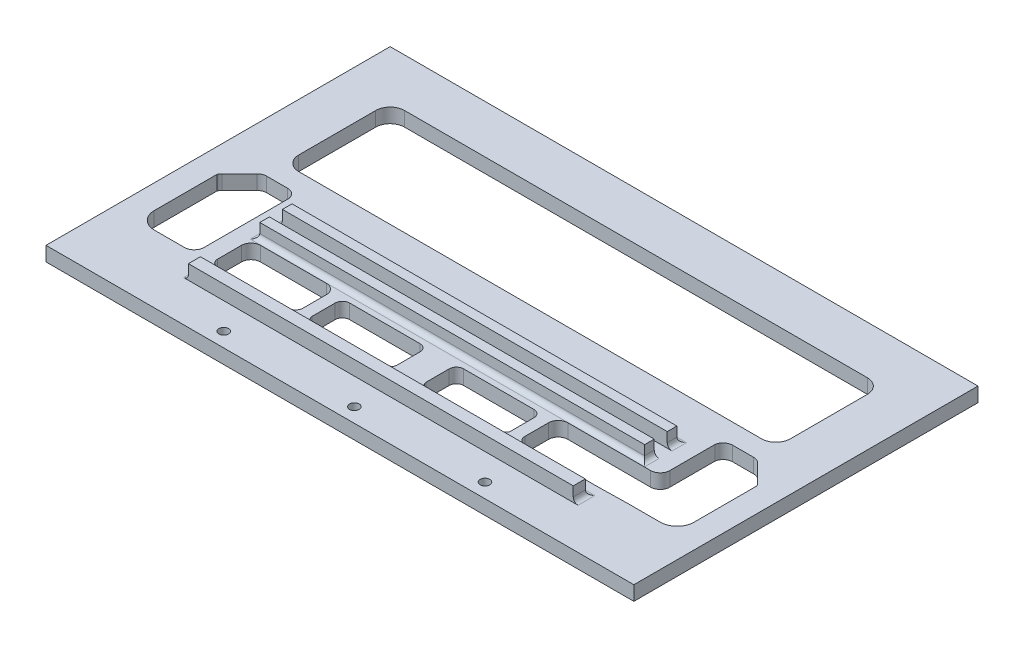
SolidWorks part; units mm, degrees
ref_plane "Front Plane" through (0, 0, 0) normal (0, 0, 1) x (1, 0, 0)
ref_plane "Top Plane" through (0, 0, 0) normal (0, 1, 0) x (1, 0, 0)
ref_plane "Right Plane" through (0, 0, 0) normal (1, 0, 0) x (0, 0, -1)
sketch "Sketch1" plane through (0, 0, 0) normal (0, 1, 0) x (1, 0, 0)
  line L1 (-61.1, -32.77) -> (61.1, -32.77)
  line L2 (-61.1, -32.77) -> (-61.1, 32.77)
  line L3 (-61.1, 32.77) -> (61.1, 32.77)
  line L4 (61.1, -32.77) -> (61.1, 32.77)
  line L5 (-61.1, -32.77) -> (61.1, 32.77) construction
  line L6 (-61.1, 32.77) -> (61.1, -32.77) construction
  point P0 (0, 0)
  dimension "D1" = 122.2
  dimension "D2" = 65.54
extrude "Boss-Extrude1" add sketch "Sketch1" along normal blind 3
ref_plane "Plane1" through (0, 0, 0) normal (-1, 0, 0) x (0, 0, 1)
sketch "Sketch2" plane through (0, 3, 0) normal (0, 1, 0) x (1, 0, 0)
  line L1 (61.1, 32.77) -> (-61.1, 32.77) construction
  line L2 (61.1, -32.77) -> (61.1, 32.77) construction
  line L3 (61.1, -27.02) -> (61.1, -29.52)
  line L5 (40, -8.73) -> (-40, -8.73)
  line L6 (40, -13.43) -> (40, -15.43)
  line L9 (-40, -8.73) -> (-40, -10.73)
  line L10 (-40, -10.73) -> (40, -10.73)
  line L11 (40, -10.73) -> (40, -8.73)
  line L12 (40, -15.43) -> (-40, -15.43)
  line L13 (-40, -15.43) -> (-40, -13.43)
  line L14 (-40, -13.43) -> (40, -13.43)
  line L15 (0, 1.65) -> (0, -1.65) construction
  point P16 (0, -15.43)
  dimension "D3" = 43.5
  dimension "D5" = 2
  dimension "D6" = 2.7
  dimension "D7" = 2
  dimension "D8" = 80
  dimension "D9" = 80
extrude "Boss-Extrude2" add sketch "Sketch2" along normal blind 10 contours L14 L13 L12 L6 | L10 L11 L5 L9 region at (0, 3, 9.73) region at (0, 3, 14.43)
fillet "Fillet1" radius 1 6 edges at (-40, 3, 9.73) (-40, 3, 14.43) (40, 3, 14.43) (40, 3, 9.73) (0, 3, 8.73) (0, 3, 15.43)
sketch "Sketch3" plane through (0, 13, 0) normal (0, 1, 0) x (1, 0, 0)
  line L0 (-40, -10.73) -> (40, -10.73) construction
  line L1 (40, -10.73) -> (40, -8.73) construction
  line L2 (40, -8.73) -> (-40, -8.73) construction
  line L3 (-40, -8.73) -> (-40, -10.73) construction
  line L4 (40, -13.43) -> (-40, -13.43) construction
  line L5 (-40, -13.43) -> (-40, -15.43) construction
  line L6 (-40, -15.43) -> (40, -15.43) construction
  line L7 (40, -15.43) -> (40, -13.43) construction
  line L8 (-40, -10.73) -> (40, -10.73)
  line L9 (40, -10.73) -> (40, -8.73)
  line L10 (40, -8.73) -> (-40, -8.73)
  line L11 (-40, -8.73) -> (-40, -10.73)
  line L12 (40, -13.43) -> (-40, -13.43)
  line L13 (-40, -13.43) -> (-40, -15.43)
  line L14 (-40, -15.43) -> (40, -15.43)
  line L15 (40, -15.43) -> (40, -13.43)
extrude "Cut-Extrude1" cut sketch "Sketch3" against normal blind 7
sketch "Sketch4" plane through (0, 3, 0) normal (0, 1, 0) x (1, 0, 0)
  line L0 (40, -30.27) -> (-40, -30.27)
  line L1 (-40, -30.27) -> (-40, -27.77)
  line L2 (-40, -27.77) -> (40, -27.77)
  line L3 (40, -27.77) -> (40, -30.27)
  line L4 (-61.1, -32.77) -> (61.1, -32.77) construction
  line L5 (0, 1.65) -> (0, -1.65) construction
  line L6 (40, -15.43) -> (40, -13.43) construction
  point P6 (0, -27.77)
  dimension "D1" = 2.5
  dimension "D2" = 2.5
extrude "Boss-Extrude3" add sketch "Sketch4" along normal up to surface (3 mm away) up to face at (0, 6, 14.43)
fillet "Fillet2" radius 1 3 edges at (-40, 3, 29.02) (40, 3, 29.02) (0, 3, 27.77)
mirror "Mirror1" about plane through (0, 0, 0) normal (-1, 0, 0) of "Boss-Extrude3"
sketch "Sketch5" plane through (0, 3, 0) normal (0, 1, 0) x (1, 0, 0)
  line L0 (48.1, 22.77) -> (6.3115, 22.77)
  line L1 (6.3115, 22.77) -> (-48.1, 22.77)
  line L2 (-51.1, 19.77) -> (-51.1, 3.77)
  line L3 (-48.1, 0.77) -> (48.1, 0.77)
  line L4 (51.1, 3.77) -> (51.1, 19.77)
  line L5 (61.1, 32.77) -> (-61.1, 32.77) construction
  line L6 (61.1, -32.77) -> (61.1, 32.77) construction
  line L7 (-61.1, 32.77) -> (-61.1, -32.77) construction
  arc A0 (-51.1, 3.77) -> (-48.1, 0.77) centre (-48.1, 3.77) ccw
  arc A1 (-48.1, 22.77) -> (-51.1, 19.77) centre (-48.1, 19.77) ccw
  arc A2 (48.1, 22.77) -> (51.1, 19.77) centre (48.1, 19.77) cw
  arc A3 (48.1, 0.77) -> (51.1, 3.77) centre (48.1, 3.77) ccw
  dimension "D5" = 3
  dimension "D1" = 10
  dimension "D2" = 10
  dimension "D3" = 10
  dimension "D4" = 22
extrude "Cut-Extrude2" cut sketch "Sketch5" against normal blind 10
sketch "Sketch6" plane through (0, 3, 0) normal (0, 1, 0) x (1, 0, 0)
  line L0 (46.3278, -24.7697) -> (39.2847, -24.8936)
  line L1 (-25.0742, -16.4735) -> (-38.7847, -16.4735)
  line L2 (38.7847, -16.4735) -> (44.2847, -16.4735)
  line L3 (55.6879, -7.6145) -> (52.0411, -3.9677)
  line L4 (50.6269, -3.3819) -> (46.2578, -3.3819)
  line L5 (56.1, -8.2136) -> (56.1, -21.2697)
  line L6 (52.6, -24.7697) -> (46.3278, -24.7697)
  line L7 (44.2847, -16.4735) -> (44.2847, -5.0547)
  line L10 (38.7847, -16.4735) -> (25.0742, -16.4735)
  line L16 (4.044, -24.8936) -> (19.6609, -24.8936)
  line L18 (39.2847, -24.8936) -> (24.5742, -24.8936)
  line L19 (23.0742, -23.3936) -> (23.0742, -18.4735)
  line L21 (20.6609, -23.8936) -> (20.6609, -19.0963)
  line L22 (19.1609, -17.5963) -> (4.544, -17.5963)
  line L23 (3.044, -19.0963) -> (3.044, -23.8936)
  line L25 (61.1, -32.77) -> (61.1, 32.77) construction
  line L26 (0, -47.4967) -> (0, 52.968) construction
  line L29 (-4.044, -24.8936) -> (-19.6609, -24.8936)
  line L31 (-3.044, -19.0963) -> (-3.044, -23.8936)
  line L33 (-19.1609, -17.5963) -> (-4.544, -17.5963)
  line L34 (-20.6609, -23.8936) -> (-20.6609, -19.0963)
  line L37 (-39.2847, -24.8936) -> (-24.5742, -24.8936)
  line L40 (-23.0742, -18.4735) -> (-23.0742, -23.3936)
  line L42 (-40.7847, -23.3936) -> (-40.7847, -18.4735)
  line L43 (-44.2847, -5.0547) -> (-44.2847, -22.7266)
  line L44 (-50.6269, -3.3819) -> (-46.2578, -3.3819)
  line L45 (-55.6879, -7.6145) -> (-52.0411, -3.9677)
  line L46 (-56.1, -21.2697) -> (-56.1, -8.2136)
  line L51 (-52.6, -24.7697) -> (-46.3278, -24.7697)
  arc A0 (-38.7847, -16.4735) -> (-40.7847, -18.4735) centre (-38.7847, -18.4735) ccw
  arc A1 (44.2847, -5.0547) -> (46.2578, -3.3819) centre (46.2578, -5.3819) cw
  arc A2 (52.0411, -3.9677) -> (50.6269, -3.3819) centre (50.6269, -5.3819) ccw
  arc A3 (56.1, -8.2136) -> (55.6879, -7.6145) centre (54.2737, -9.0287) ccw
  arc A4 (-25.0742, -16.4735) -> (-23.0742, -18.4735) centre (-25.0742, -18.4735) cw
  arc A6 (23.0742, -18.4735) -> (25.0742, -16.4735) centre (25.0742, -18.4735) cw
  arc A8 (56.1, -21.2697) -> (52.6, -24.7697) centre (52.6, -21.2697) cw
  arc A10 (4.544, -17.5963) -> (3.044, -19.0963) centre (4.544, -19.0963) ccw
  arc A11 (20.6609, -19.0963) -> (19.1609, -17.5963) centre (19.1609, -19.0963) ccw
  arc A15 (24.5742, -24.8936) -> (23.0742, -23.3936) centre (24.5742, -23.3936) cw
  arc A16 (39.3374, -24.8927) -> (39.2847, -24.8936) centre (39.2847, -23.3936) cw
  arc A18 (3.044, -23.8936) -> (4.044, -24.8936) centre (4.044, -23.8936) ccw
  arc A19 (20.6609, -23.8936) -> (19.6609, -24.8936) centre (19.6609, -23.8936) cw
  arc A26 (-3.044, -23.8936) -> (-4.044, -24.8936) centre (-4.044, -23.8936) cw
  arc A27 (-20.6609, -23.8936) -> (-19.6609, -24.8936) centre (-19.6609, -23.8936) ccw
  arc A29 (-4.544, -17.5963) -> (-3.044, -19.0963) centre (-4.544, -19.0963) cw
  arc A31 (-20.6609, -19.0963) -> (-19.1609, -17.5963) centre (-19.1609, -19.0963) cw
  arc A35 (-40.7847, -23.3936) -> (-39.2847, -24.8936) centre (-39.2847, -23.3936) ccw
  arc A36 (-24.5742, -24.8936) -> (-23.0742, -23.3936) centre (-24.5742, -23.3936) ccw
  arc A41 (-44.2847, -5.0547) -> (-46.2578, -3.3819) centre (-46.2578, -5.3819) ccw
  arc A43 (-52.0411, -3.9677) -> (-50.6269, -3.3819) centre (-50.6269, -5.3819) cw
  arc A44 (-56.1, -8.2136) -> (-55.6879, -7.6145) centre (-54.2737, -9.0287) cw
  arc A46 (-46.3278, -24.7697) -> (-44.2847, -22.7266) centre (-46.3278, -22.7266) ccw
  arc A49 (-56.1, -21.2697) -> (-52.6, -24.7697) centre (-52.6, -21.2697) ccw
  point P3 (-40.7847, -16.4735)
  point P12 (-23.0742, -16.4735)
  point P17 (23.0742, -16.4735)
  point P27 (40.7847, -16.4735)
  point P66 (3.044, -22.0111)
  point P71 (20.6609, -24.8936)
  point P74 (20.6609, -22.0111)
  dimension "D2" = 2
  dimension "D1" = 5
extrude "Cut-Extrude3" cut sketch "Sketch6" against normal blind 10 contours A15 L18 L0 L6 A8 L5 A3 L3 A2 L4 A1 L7 L2 L10 A6 L19 | A19 L21 A11 L22 A10 L23 A18 L16 | A31 L34 A27 L29 A26 L31 A29 L33 | L46 A49 L51 A46 L43 A41 L44 A43 L45 A44 | L37 A36 L40 A4 L1 A0 L42 A35 region at (43.0478, 3, 17.0909) region at (11.8524, 3, 21.2586) region at (-11.8524, 3, 21.2586) region at (-49.9758, 3, 14.3824)
sketch "Sketch7" plane through (0, 0, 32.77) normal (0, 0, 1) x (1, 0, 0)
  line L4 (-61.1, 0) -> (61.1, 0)
  line L5 (61.1, 0) -> (61.1, 3)
  line L6 (61.1, 3) -> (-61.1, 3)
  line L7 (-61.1, 3) -> (-61.1, 0)
  line L8 (-61.1, 0) -> (61.1, 0)
  line L9 (61.1, 0) -> (61.1, 3)
  line L10 (61.1, 3) -> (-61.1, 3)
  line L11 (-61.1, 3) -> (-61.1, 0)
  dimension "D1" = 0
extrude "Boss-Extrude4" add sketch "Sketch7" along normal blind 6
sketch "Sketch8" plane through (0, 0, 0) normal (0, -1, 0) x (1, 0, 0)
  line L0 (-61.1, 38.77) -> (61.1, 38.77) construction
  line L1 (-61.1, -32.77) -> (-61.1, 38.77) construction
  line L2 (61.1, 38.77) -> (61.1, -32.77) construction
  circle A0 centre (0, 35.77) radius 1
  circle A1 centre (-27.15, 35.77) radius 1
  circle A2 centre (27.15, 35.77) radius 1
  dimension "D1" = 2
  dimension "D4" = 2
  dimension "D5" = 2
  dimension "D2" = 3
  dimension "D3" = 3
  dimension "D6" = 33.95
  dimension "D7" = 33.95
extrude "Cut-Extrude4" cut sketch "Sketch8" against normal blind 6
fillet "Fillet3" radius 2 1 edges at (44.2847, 1.5, 16.4735)
